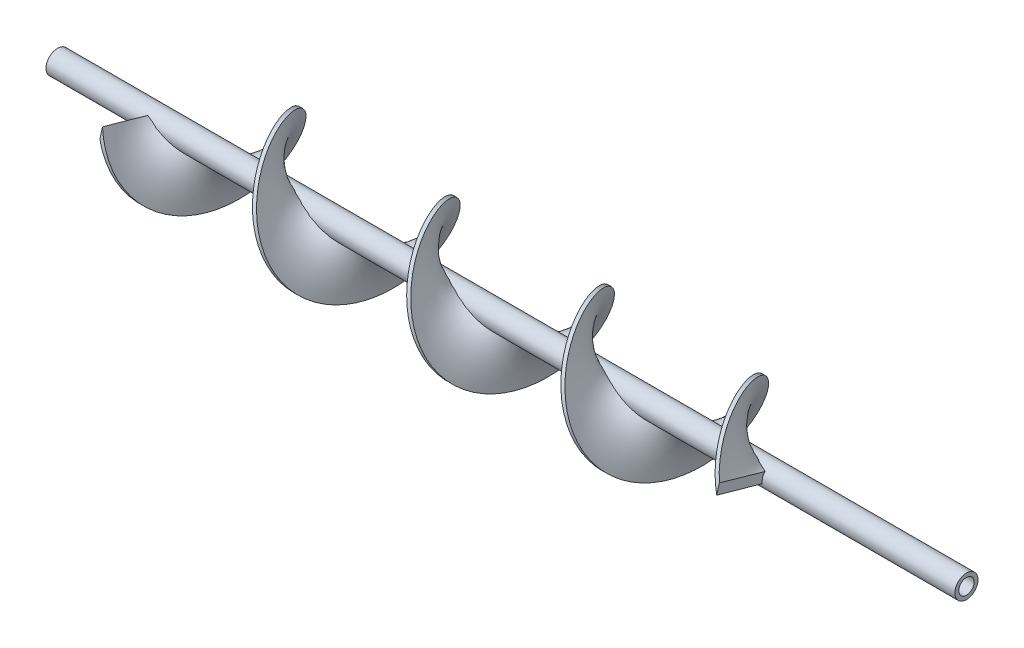
SolidWorks part; units mm, degrees
material "Brass"
ref_plane "Vorderansicht" through (0, 0, 0) normal (0, 0, 1) x (1, 0, 0)
ref_plane "Draufsicht" through (0, 0, 0) normal (0, 1, 0) x (1, 0, 0)
ref_plane "Seitenansicht" through (0, 0, 0) normal (1, 0, 0) x (0, 0, -1)
sketch "Skizze3" plane through (0, 0, 0) normal (1, 0, 0) x (0, 0, -1)
  circle A0 centre (0, 0) radius 6
  circle A1 centre (0, 0) radius 4
  dimension "D1" = 12
  dimension "D2" = 2
extrude "Aufsatz-Linear austragen1" add sketch "Skizze3" against normal blind 415 and the other way blind 51.5 separate body
ref_plane "Ref_of_Spiral" through (36.5, 0, 0) normal (1, 0, 0) x (0, 0, -1)
sketch "Skizze1" plane through (36.5, 0, 0) normal (1, 0, 0) x (0, 0, -1)
  circle A0 centre (0, 0) radius 4
  dimension "D1" = 8
curve "Spirale/Helix1" pitch 80 height 320 radius 4 centre (36.5, 0, 0) axis (-1, 0, 0) start towards (0, 0, -1)
sketch "Skizze2" plane through (0, 0, 0) normal (1, 0, 0) x (0, 0, -1)
  line L0 (19.3938, 0) -> (56.2084, 0) construction
  line L2 (3.1225, -2.5) -> (30, -2.5)
  line L4 (3.1225, 2.5) -> (30, 2.5)
  line L5 (30, -2.5) -> (30, 2.5)
  arc A1 (3.1225, -2.5) -> (3.1225, 2.5) centre (0, 0) ccw
  dimension "D1" = 30
  dimension "D3" = 5
sweep "Austragung1" add profiles "Skizze2" path "Spirale/Helix1"
sketch "Sketch1" plane through (51.5, 0, 0) normal (1, 0, 0) x (0, 0, -1)
  circle A0 centre (0, 0) radius 4
  circle A1 centre (0, 0) radius 6
extrude "Boss-Extrude1" add sketch "Sketch1" along normal blind 65
sketch "Sketch2" plane through (-415, 0, 0) normal (-1, 0, 0) x (0, 0, 1)
  circle A0 centre (0, 0) radius 6
extrude "Cut-Extrude1" cut sketch "Sketch2" against normal blind 80
sketch "Sketch3" plane through (116.5, 0, 0) normal (1, 0, 0) x (0, 0, -1)
  circle A0 centre (0, 0) radius 6
  circle A1 centre (0, 0) radius 4
extrude "Boss-Extrude2" add sketch "Sketch3" along normal blind 20
